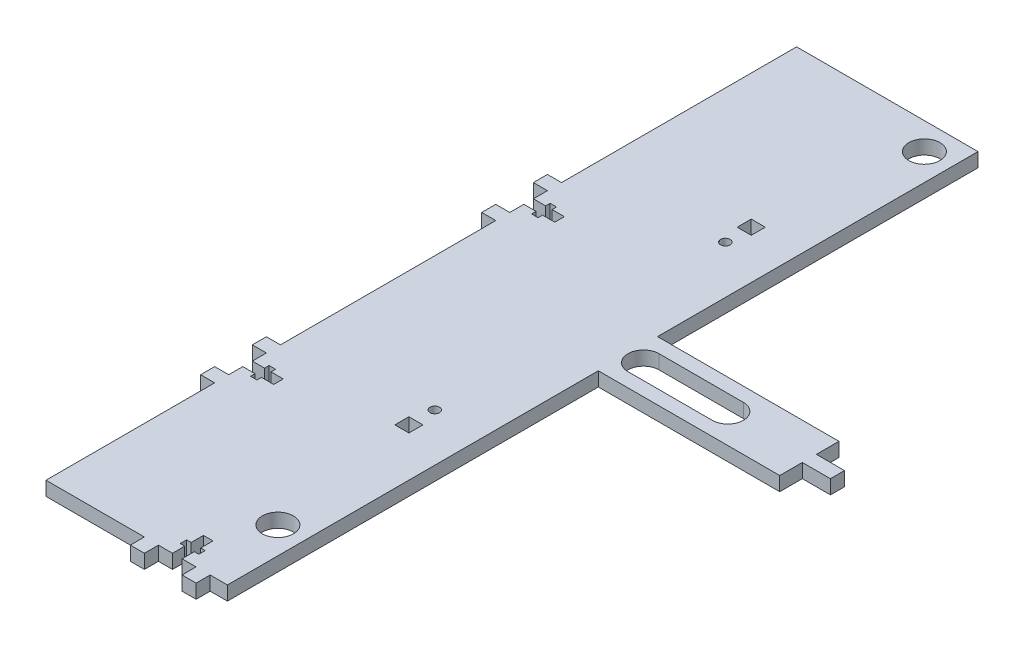
SolidWorks part; units mm, degrees
ref_plane "Front Plane" through (0, 0, 0) normal (0, 0, 1) x (1, 0, 0)
ref_plane "Top Plane" through (0, 0, 0) normal (0, 1, 0) x (1, 0, 0)
ref_plane "Right Plane" through (0, 0, 0) normal (1, 0, 0) x (0, 0, -1)
sketch "Axle Support Plate" plane through (0, 0, 0) normal (0, 1, 0) x (1, 0, 0)
  line L0 (25.4, 146.05) -> (25.4, -146.05) construction
  line L1 (12.7, 158.1601) -> (12.7, -187.325) construction
  line L2 (12.7, -80.518) -> (12.7, -74.168)
  line L3 (12.7, 80.518) -> (19.05, 80.518)
  line L4 (37.5101, -180.975) -> (37.5101, -13.3801)
  line L5 (0, 0) -> (37.5101, 158.1601) construction
  line L6 (0, 0) -> (37.5101, -180.975) construction
  line L7 (-44.45, -75.057) -> (-44.45, 22.225)
  line L8 (-44.45, 158.1601) -> (37.5101, 158.1601)
  line L9 (6.35, -180.975) -> (12.7, -180.975)
  line L10 (12.7, 80.518) -> (12.7, 74.168)
  line L11 (12.7, 74.168) -> (19.05, 74.168)
  line L12 (0, -187.325) -> (0, -180.975)
  line L13 (19.05, 80.518) -> (19.05, 74.168)
  line L14 (12.7, -80.518) -> (19.05, -80.518)
  line L15 (19.05, -80.518) -> (19.05, -74.168)
  line L16 (12.7, -74.168) -> (19.05, -74.168)
  line L17 (37.5101, 0) -> (0, 0) construction
  line L18 (0, -187.325) -> (6.35, -187.325)
  line L19 (6.35, -187.325) -> (6.35, -180.975)
  line L20 (23.368, -180.975) -> (23.368, -187.325)
  line L21 (23.368, -187.325) -> (29.718, -187.325)
  line L22 (29.718, -187.325) -> (29.718, -180.975)
  line L23 (29.718, -180.975) -> (37.5101, -180.975)
  line L24 (15.875, 80.518) -> (15.875, 65.659) construction
  line L25 (12.7, -180.975) -> (12.7, -175.44)
  line L26 (12.7, -175.44) -> (10.659, -175.44)
  line L27 (10.659, -175.44) -> (10.659, -172.54)
  line L28 (10.659, -172.54) -> (12.7, -172.54)
  line L29 (12.7, -172.54) -> (12.7, -167.005)
  line L30 (12.7, -167.005) -> (17.018, -167.005)
  line L31 (17.018, -167.005) -> (17.018, -172.54)
  line L32 (17.018, -172.54) -> (19.059, -172.54)
  line L33 (19.059, -172.54) -> (19.059, -175.44)
  line L34 (19.059, -175.44) -> (17.018, -175.44)
  line L35 (17.018, -175.44) -> (17.018, -180.975)
  line L36 (17.018, -180.975) -> (23.368, -180.975)
  line L37 (37.5101, 13.3801) -> (119.4703, 13.3801)
  line L38 (119.4703, 13.3801) -> (119.4703, 3.175)
  line L39 (119.4703, -13.3801) -> (37.5101, -13.3801)
  line L40 (44.5403, 0) -> (82.6403, 0) construction
  line L41 (44.5403, 7.0301) -> (82.6403, 7.0301)
  line L42 (44.5403, -7.0301) -> (82.6403, -7.0301)
  line L43 (119.4703, -3.175) -> (132.1703, -3.175)
  line L44 (132.1703, -3.175) -> (132.1703, 3.175)
  line L45 (132.1703, 3.175) -> (119.4703, 3.175)
  line L46 (37.5101, 13.3801) -> (37.5101, 158.1601)
  line L47 (37.5101, 13.3801) -> (37.5101, -13.3801) construction
  line L48 (37.5101, 0) -> (132.1703, 0) construction
  line L51 (119.4703, -3.175) -> (119.4703, -13.3801)
  line L81 (-44.45, 51.943) -> (-44.45, 158.1601)
  line L90 (0, -180.975) -> (-44.45, -180.975)
  line L94 (-44.45, -180.975) -> (-44.45, -104.775)
  circle A0 centre (25.4, 146.05) radius 7.0301
  circle A1 centre (25.4, -146.05) radius 7.0301
  circle A2 centre (15.875, 65.659) radius 2.159
  circle A3 centre (15.875, -65.659) radius 2.159
  arc A4 (44.5403, 7.0301) -> (44.5403, -7.0301) centre (44.5403, 0) ccw
  arc A5 (82.6403, -7.0301) -> (82.6403, 7.0301) centre (82.6403, 0) ccw
  point P0 (0, 0)
  point P15 (25.4, 0)
  point P38 (15.875, 67.818)
  point P57 (63.5903, 0)
  line B0 (-44.45, -81.407) -> (-50.8, -81.407)
  line B1 (-50.8, -81.407) -> (-50.8, -75.057)
  line B2 (-50.8, -75.057) -> (-44.45, -75.057)
  line B3 (-44.45, -87.757) -> (-38.915, -87.757)
  line B4 (-38.915, -87.757) -> (-38.915, -85.716)
  line B5 (-38.915, -85.716) -> (-36.015, -85.716)
  line B6 (-36.015, -85.716) -> (-36.015, -87.757)
  line B7 (-36.015, -87.757) -> (-30.48, -87.757)
  line B8 (-30.48, -87.757) -> (-30.48, -92.075)
  line B9 (-30.48, -92.075) -> (-36.015, -92.075)
  line B10 (-36.015, -92.075) -> (-36.015, -94.116)
  line B11 (-36.015, -94.116) -> (-38.915, -94.116)
  line B12 (-38.915, -94.116) -> (-38.915, -92.075)
  line B13 (-38.915, -92.075) -> (-44.45, -92.075)
  line B14 (-30.48, -89.916) -> (-44.45, -89.916) construction
  line B15 (-44.45, -98.425) -> (-44.45, -92.075)
  line B16 (-50.8, -104.775) -> (-44.45, -104.775)
  line B17 (-44.45, -81.407) -> (-44.45, -87.757)
  line B18 (-50.8, -98.425) -> (-50.8, -104.775)
  line B19 (-44.45, -98.425) -> (-50.8, -98.425)
  line B20 (-44.45, 45.593) -> (-50.8, 45.593)
  line B21 (-50.8, 45.593) -> (-50.8, 51.943)
  line B22 (-50.8, 51.943) -> (-44.45, 51.943)
  line B23 (-44.45, 39.243) -> (-38.915, 39.243)
  line B24 (-38.915, 39.243) -> (-38.915, 41.284)
  line B25 (-38.915, 41.284) -> (-36.015, 41.284)
  line B26 (-36.015, 41.284) -> (-36.015, 39.243)
  line B27 (-36.015, 39.243) -> (-30.48, 39.243)
  line B28 (-30.48, 39.243) -> (-30.48, 34.925)
  line B29 (-30.48, 34.925) -> (-36.015, 34.925)
  line B30 (-36.015, 34.925) -> (-36.015, 32.884)
  line B31 (-36.015, 32.884) -> (-38.915, 32.884)
  line B32 (-38.915, 32.884) -> (-38.915, 34.925)
  line B33 (-38.915, 34.925) -> (-44.45, 34.925)
  line B34 (-30.48, 37.084) -> (-44.45, 37.084) construction
  line B35 (-44.45, 28.575) -> (-44.45, 34.925)
  line B36 (-50.8, 22.225) -> (-44.45, 22.225)
  line B37 (-44.45, 45.593) -> (-44.45, 39.243)
  line B38 (-50.8, 28.575) -> (-50.8, 22.225)
  line B39 (-44.45, 28.575) -> (-50.8, 28.575)
  dimension "D1" = 5.08
  dimension "D4" = 14.0603
  dimension "D5" = 5.08
  dimension "D8" = 63.5
  dimension "D14" = 14.0603
  dimension "D15" = 4.318
  dimension "D16" = 6.35
  dimension "D22" = 7.0301
  dimension "D25" = 36.83
  dimension "D2" = 292.1
  dimension "D3" = 6.35
  dimension "D6" = 12.7
  dimension "D7" = 6.35
  dimension "D9" = 12.7
  dimension "D10" = 6.35
  dimension "D11" = 6.35
  dimension "D12" = 13.97
  dimension "D13" = 34.925
  dimension "D17" = 4.318
  dimension "D18" = 8.4
  dimension "D19" = 2.9
  dimension "D20" = 6.35
  dimension "D21" = 6.35
  dimension "D23" = 6.35
  dimension "D24" = 38.1
  dimension "D26" = 12.7
  dimension "D27" = 6.35
  dimension "D28" = 69.85
  dimension "D29" = 76.2
  dimension "D30" = 203.2
sketch_block_instance "Male T-slot assembly-1"
sketch_block "Male T-slot assembly" parameters "D1"=6.35, "D2"=6.35, "D3"=4.318, "D4"=2.9, "D5"=8.4, "D6"=13.97, "D7"=6.35
sketch_block_instance "Male T-slot assembly-2"
extrude "Boss-Extrude1" add sketch "Axle Support Plate" along normal blind 6.35 contours L12 L18 L19 L9 L25 L26 L27 L28 L29 L30 L31 L32 L33 L34 L35 L36 L20 L21 L22 L23 L4 L39 L51 L43 L44 L45 L38 L37 L46 L8 region at (1.0395, 0, 11.0345)
equation "\"Ball Diameter\"= 1.75in"
equation "\"Sheet Thickness\"= 0.25in"
equation "\"Screw Diameter\"= .17in"
equation "\"Robot Diameter\"= 14in"
equation "\"Castor Screw Diameter\"= 0.22in"
equation "\"Wheel Diameter\" = 4in"
equation "\"Nut Diameter\" = 8.4mm"
equation "\"Nut Height\" = 2.9mm"
equation "\"Screw Height\" = 0.55in"
equation "\"Pulley Diameter\" = 1in"
equation "\"Reactor Height\" = 14in"
equation "\"Elevator Height\" = 11.5in"
equation "\"Elevator Width\" = \"Ball Diameter\" + 0.25in"
equation "\"D1@Boss-Extrude1\"=\"Sheet Thickness\""
equation "\"Elevator Bearing Diameter\" = sqr(2*(\"Sheet Thickness\"^2)) + 0.2in"
equation "\"Elevator Axle Length\" = \"Elevator Width\" + 8*\"Sheet Thickness\""
equation "\"D4@Axle Support Plate\"=\"Elevator Bearing Diameter\""
equation "\"D6@Axle Support Plate\"=(\"Pulley Diameter\")/2"
equation "\"D3@Axle Support Plate\"=\"Sheet Thickness\""
equation "\"D7@Axle Support Plate\"=\"Sheet Thickness\""
equation "\"D10@Axle Support Plate\"=\"Sheet Thickness\""
equation "\"D11@Axle Support Plate\"=\"Sheet Thickness\""
equation "\"D12@Axle Support Plate\"=\"Screw Height\""
equation "\"D13@Axle Support Plate\"=2.5in - \"Sheet Thickness\" - (\"Ball Diameter\")/2"
equation "\"D9@Axle Support Plate\"=2*\"Sheet Thickness\""
equation "\"D14@Axle Support Plate\"=\"Elevator Bearing Diameter\""
equation "\"D15@Axle Support Plate\"=\"Screw Diameter\""
equation "\"D16@Axle Support Plate\"=\"Sheet Thickness\""
equation "\"D17@Axle Support Plate\"=\"Screw Diameter\""
equation "\"D18@Axle Support Plate\"=\"Nut Diameter\""
equation "\"D19@Axle Support Plate\"=\"Nut Height\""
equation "\"D20@Axle Support Plate\"=\"Sheet Thickness\""
equation "\"D21@Axle Support Plate\"=\"Sheet Thickness\""
equation "\"D22@Axle Support Plate\"=\"Elevator Bearing Diameter\"/2"
equation "\"D23@Axle Support Plate\"=\"Sheet Thickness\""
equation "\"Elevator Axle Endcap Diameter\" = \"Pulley Diameter\" + 0.25in"
equation "\"D25@Axle Support Plate\"=\"Elevator Axle Endcap Diameter\"+0.2in"
equation "\"D27@Axle Support Plate\"=\"Sheet Thickness\""
equation "\"Elevator Clearance from Axis\" = (\"Pulley Diameter\"/2) + \"Ball Diameter\" + 0.5in"
equation "\"D28@Axle Support Plate\"=\"Elevator Clearance from Axis\""
